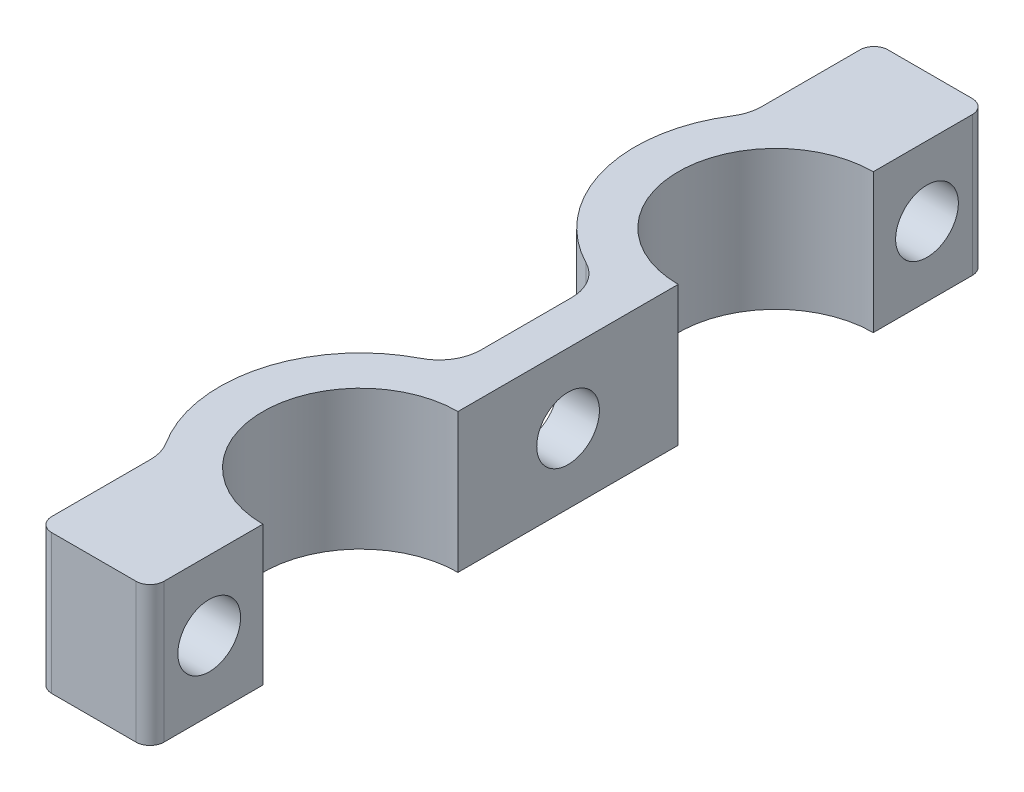
SolidWorks part; units mm, degrees
material "3.1355 (EN-AW 2024)"
ref_plane "Front" through (0, 0, 0) normal (0, 0, 1) x (1, 0, 0)
ref_plane "Top" through (0, 0, 0) normal (0, 1, 0) x (1, 0, 0)
ref_plane "Right" through (0, 0, 0) normal (1, 0, 0) x (0, 0, -1)
sketch "Эскиз1" plane through (0, 0, 0) normal (0, 1, 0) x (1, 0, 0)
  line L0 (0, 0) -> (0, 60) construction
  line L1 (0, 30) -> (-15.0292, 30) construction
  line L2 (0, 0) -> (0, 8)
  line L3 (0, 60) -> (0, 52)
  line L4 (0, 37.8) -> (0, 22.2)
  line L5 (-3, 0) -> (-3, 5.4558)
  line L6 (-3, 35.2558) -> (-3, 24.7442)
  line L7 (-3, 60) -> (-3, 54.5442)
  line L8 (-3, 60) -> (0, 60)
  line L9 (-3, 0) -> (0, 0)
  circle A0 centre (0, 15.1) radius 7.1 construction
  circle A1 centre (0, 44.9) radius 7.1 construction
  arc A2 (0, 8) -> (0, 22.2) centre (0, 15.1) cw
  arc A3 (0, 52) -> (0, 37.8) centre (0, 44.9) ccw
  arc A4 (-3, 5.4558) -> (-3, 24.7442) centre (0, 15.1) cw
  arc A5 (-3, 54.5442) -> (-3, 35.2558) centre (0, 44.9) ccw
  point P9 (0, 22.2)
  dimension "D2" = 15.1
  dimension "D3" = 14.2
  dimension "D1" = 60
  dimension "D4" = 3
extrude "Бобышка-Вытянуть1" add sketch "Эскиз1" along normal blind 10
sketch "Эскиз2" plane through (0, 10, 0) normal (0, 1, 0) x (1, 0, 0)
  line L0 (-3, 60) -> (-8.0498, 60)
  line L1 (-8.0498, 60) -> (-8.0498, 51)
  line L2 (-3, 60) -> (-3, 54.5442)
  line L3 (0, 30) -> (-3, 30) construction
  line L4 (0, 22.2) -> (0, 37.8) construction
  line L5 (-3, 35.2558) -> (-3, 24.7442) construction
  line L6 (-3, 0) -> (-3, 5.4558)
  line L7 (-8.0498, 0) -> (-8.0498, 9)
  line L8 (-3, 0) -> (-8.0498, 0)
  arc A0 (-3, 54.5442) -> (-3, 35.2558) centre (0, 44.9) ccw construction
  arc A1 (-3, 54.5442) -> (-8.0498, 51) centre (0, 44.9) ccw
  arc A2 (-3, 5.4558) -> (-8.0498, 9) centre (0, 15.1) cw
  dimension "D1" = 9
sketch "Эскиз3" plane through (-3, 0, 0) normal (-1, 0, 0) x (0, 0, 1)
  line L0 (-60, 5) -> (-54.7288, 5) construction
  line L1 (-60, 10) -> (-60, 0) construction
  line L3 (-30, 10) -> (-30, 0) construction
  line L4 (-35.2558, 10) -> (-24.7442, 10) construction
  line L5 (-35.2558, 0) -> (-24.7442, 0) construction
  circle A0 centre (-55.75, 5) radius 2.25
  circle A1 centre (-4.25, 5) radius 2.25
  point P6 (-58, 5)
  point P7 (-53.5, 5)
  dimension "D1" = 4.5
  dimension "D2" = 2
extrude "Бобышка-Вытянуть2" add sketch "Эскиз2" against normal up to surface (10 mm away) up to face at (-3.8667, 0, -30)
extrude "Вырез-Вытянуть1" cut sketch "Эскиз3" against normal through all and the other way up to surface (5.0498 mm away) other way up to face at (-8.0498, 5, -55.5)
sketch "Эскиз4" plane through (-3, 0, 0) normal (-1, 0, 0) x (0, 0, 1)
  line L0 (-30, 10) -> (-30, 0) construction
  line L1 (-35.2558, 10) -> (-24.7442, 10) construction
  line L2 (-35.2558, 0) -> (-24.7442, 0) construction
  circle A0 centre (-30, 5) radius 2.25
  dimension "D1" = 4.5
extrude "Вырез-Вытянуть2" cut sketch "Эскиз4" against normal through all
fillet "Скругление1" radius 3 4 edges at (-8.0498, 5, -9) (-8.0498, 5, -51) (-3, 5, -35.2558) (-3, 5, -24.7442)
fillet "Скругление2" radius 1 2 edges at (-8.0498, 5, -60) (-8.0498, 5, 0)
sketch "Эскиз5" plane through (0, 0, 0) normal (0, -1, 0) x (1, 0, 0)
  line L0 (0, -8) -> (0, -8.1)
  line L1 (0, -51.9) -> (0, -52)
  line L2 (0, -37.8) -> (0, -37.9)
  line L3 (0, -22.1) -> (0, -22.2)
  arc A0 (0, -8) -> (0, -22.2) centre (0, -15.1) ccw construction
  arc A1 (0, -37.8) -> (0, -52) centre (0, -44.9) ccw construction
  arc A2 (0, -8) -> (0, -22.2) centre (0, -15.1) ccw
  arc A3 (0, -37.8) -> (0, -52) centre (0, -44.9) ccw
  arc A4 (0, -8.1) -> (0, -22.1) centre (0, -15.1) ccw
  arc A5 (0, -37.9) -> (0, -51.9) centre (0, -44.9) ccw
  dimension "D1" = 0.1
extrude "Бобышка-Вытянуть3" add sketch "Эскиз5" against normal through all
sketch "Эскиз6" plane through (0, 0, 0) normal (0, -1, 0) x (1, 0, 0)
  line L0 (-10.1, -44.9) -> (-10.1, -60) construction
  line L1 (-7.0498, -60) -> (-10.1, -60) construction
  arc A0 (-4.626, -35.9217) -> (-8.5193, -50.325) centre (0, -44.9) ccw construction
fillet "Скругление3" radius 1 2 edges at (0, 5, -60) (0, 5, 0)
equation "\"D2@Эскиз1\"=8+\"D3@Эскиз1\"/2"
